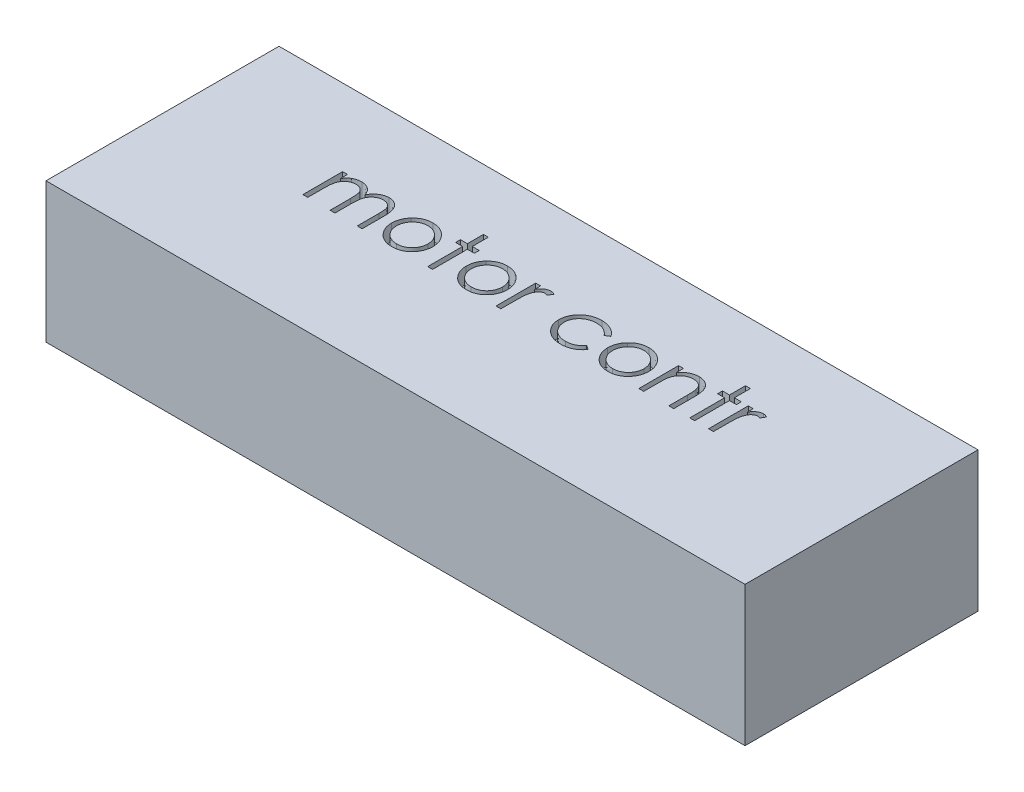
SolidWorks part; units mm, degrees
ref_plane "Front Plane" through (0, 0, 0) normal (0, 0, 1) x (1, 0, 0)
ref_plane "Top Plane" through (0, 0, 0) normal (0, 1, 0) x (1, 0, 0)
ref_plane "Right Plane" through (0, 0, 0) normal (1, 0, 0) x (0, 0, -1)
sketch "Sketch1" plane through (0, 0, 0) normal (0, 1, 0) x (1, 0, 0)
  line L1 (-22.5, -7.5) -> (22.5, -7.5)
  line L2 (-22.5, -7.5) -> (-22.5, 7.5)
  line L3 (-22.5, 7.5) -> (22.5, 7.5)
  line L4 (22.5, -7.5) -> (22.5, 7.5)
  line L5 (-22.5, -7.5) -> (22.5, 7.5) construction
  line L6 (-22.5, 7.5) -> (22.5, -7.5) construction
  point P0 (0, 0)
  dimension "D1" = 45
  dimension "D2" = 15
extrude "Boss-Extrude1" add sketch "Sketch1" along normal blind 9
sketch "Sketch2" plane through (0, 9, 0) normal (0, 1, 0) x (1, 0, 0)
  line L0 (-22.5, 0) -> (22.5, 0) construction
  line L1 (22.5, -7.5) -> (22.5, 7.5) construction
  text T0 "motor contr"
  point P6 (0, 0)
extrude "Cut-Extrude1" cut sketch "Sketch2" against normal blind 1
